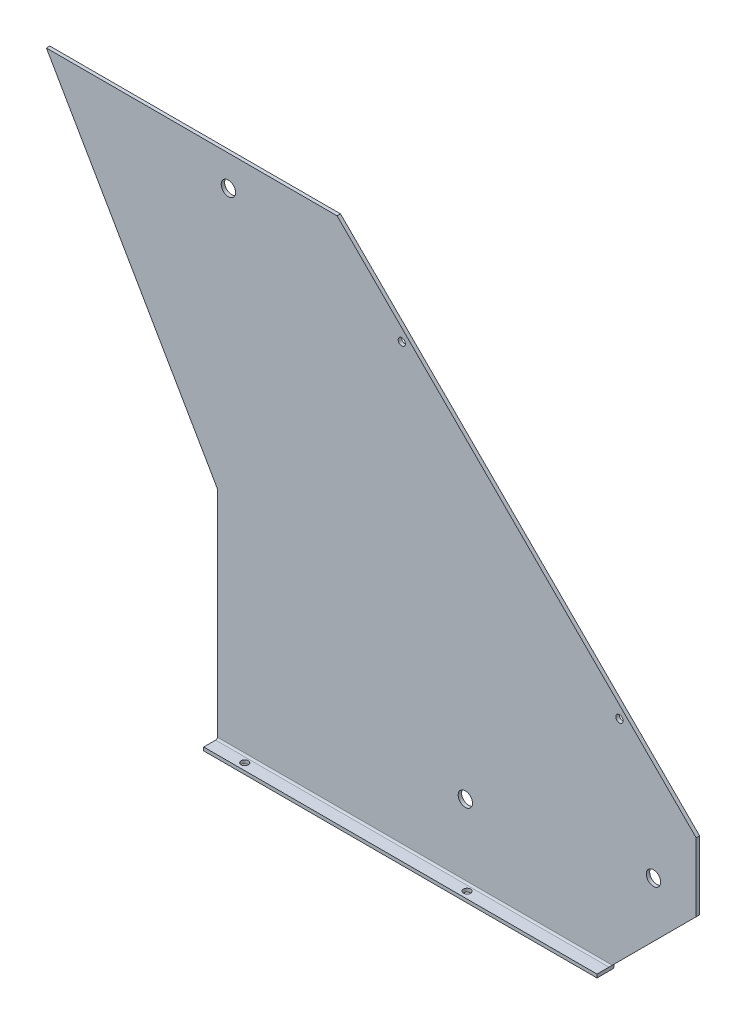
SolidWorks part; units mm, degrees
ref_plane "Plan de face" through (0, 0, 0) normal (0, 0, 1) x (1, 0, 0)
ref_plane "Plan de dessus" through (0, 0, 0) normal (0, 1, 0) x (1, 0, 0)
ref_plane "Plan de droite" through (0, 0, 0) normal (1, 0, 0) x (0, 0, -1)
sketch "Esquisse1" plane through (0, 0, 0) normal (0, 0, 1) x (1, 0, 0)
  line L0 (-70, 150) -> (140, -60)
  line L1 (-140, 150) -> (140, 150)
  line L2 (-140, -23.2051) -> (-140, -150)
  line L3 (-140, -150) -> (140, -150)
  line L4 (140, 150) -> (140, -150)
  line L5 (-140, 150) -> (140, -150) construction
  line L6 (-140, -150) -> (140, 150) construction
  line L7 (140, -100) -> (90, -150)
  line L8 (-140, 150) -> (-240, 150)
  line L9 (-240, 150) -> (-140, -23.2051)
  line L10 (-140, 150) -> (-140, -23.2051) construction
  point P0 (0, 0)
  dimension "D1" = 300
  dimension "D2" = 280
  dimension "D3" = 70
  dimension "D4" = 45
  dimension "D5" = 50
  dimension "D6" = 50
  dimension "D7" = 60
  dimension "D8" = 100
extrude "Boss.-Extru.1" add sketch "Esquisse1" along normal blind 2 contours L4 L0 L1 L2 L3 region at (-46.1183, -11.5094, 0)
sketch "Esquisse2" plane through (0, -150, 0) normal (0, -1, 0) x (1, 0, 0)
  line L0 (90, 2) -> (90, 0) construction
  line L1 (-140, 0) -> (90, 0)
  line L2 (-140, 0) -> (-140, 10)
  line L3 (-140, 10) -> (90, 10)
  line L4 (90, 0) -> (90, 10)
  dimension "D1" = 10
extrude "Boss.-Extru.2" add sketch "Esquisse2" along normal blind 2
fillet "Congé1" radius 1 2 edges at (-25, -152, 0)
sketch "Esquisse3" plane through (0, 0, 2) normal (0, 0, 1) x (1, 0, 0)
  line L0 (-133.5641, 132.1075) -> (5, -107.8925) construction
  line L1 (5, -107.8925) -> (115, -92.8925) construction
  line L2 (-303.081, -185.3925) -> (232.511, -185.3925) construction
  line L3 (5, -107.8925) -> (5, -120.3925) construction
  line L4 (-140, -152) -> (90, -152) construction
  line L5 (0, 0) -> (79.2583, 0) construction
  line L6 (0, 0) -> (0, 50.4511) construction
  line L7 (115, -92.8925) -> (115, -105.3925) construction
  circle A0 centre (-133.5641, 132.1075) radius 4.2
  circle A1 centre (5, -107.8925) radius 4.2
  circle A2 centre (115, -92.8925) radius 4.2
  circle A3 centre (-133.5641, 132.1075) radius 12.5 construction
  circle A4 centre (5, -107.8925) radius 12.5 construction
  circle A5 centre (115, -92.8925) radius 12.5 construction
  dimension "D1" = 8.4
  dimension "D2" = 25
  dimension "D3" = 65
  dimension "D4" = 33.3925
  dimension "D5" = 60
  dimension "D6" = 5
  dimension "D7" = 110
  dimension "D8" = 80
  dimension "D9" = 240
extrude "Enlèv. mat.-Extru.1" cut sketch "Esquisse3" against normal through all
sketch "Esquisse5" plane through (0, -150, 0) normal (0, 1, 0) x (1, 0, 0)
  line L0 (79.7246, -2) -> (79.7246, -10) construction
  line L1 (90, -10) -> (-140, -10) construction
  line L2 (-140, -2) -> (91, -2) construction
  line L3 (79.7246, -6) -> (12.5895, -6) construction
  line L5 (-140, -10) -> (-140, -3) construction
  circle A0 centre (10, -6) radius 2.1
  circle A1 centre (-120, -6) radius 2.1
  point P5 (79.7246, -6)
  dimension "D3" = 4.2
  dimension "D1" = 20
  dimension "D2" = 130
extrude "Enlèv. mat.-Extru.2" cut sketch "Esquisse5" against normal through all
ref_plane "Plan1" through (0, 0, -60) normal (0, 0, 1) x (1, 0, 0)
sketch "Esquisse6" plane through (0, 0, 2) normal (0, 0, 1) x (1, 0, 0)
  line L0 (-70, 150) -> (140, -60) construction
  line L1 (-32.1751, 105.1041) -> (95.1041, -22.1751) construction
  line L2 (35, 45) -> (67.7332, 77.7332) construction
  circle A0 centre (-32.1751, 105.1041) radius 2.1
  circle A1 centre (95.1041, -22.1751) radius 2.1
  point P3 (35, 45)
  dimension "D1" = 4.2
  dimension "D2" = 5
  dimension "D3" = 90
extrude "Enlèv. mat.-Extru.3" cut sketch "Esquisse6" against normal through all contours A1 | A0 region at (-32.1751, 105.1041, 2) region at (95.1041, -22.1751, 2)
